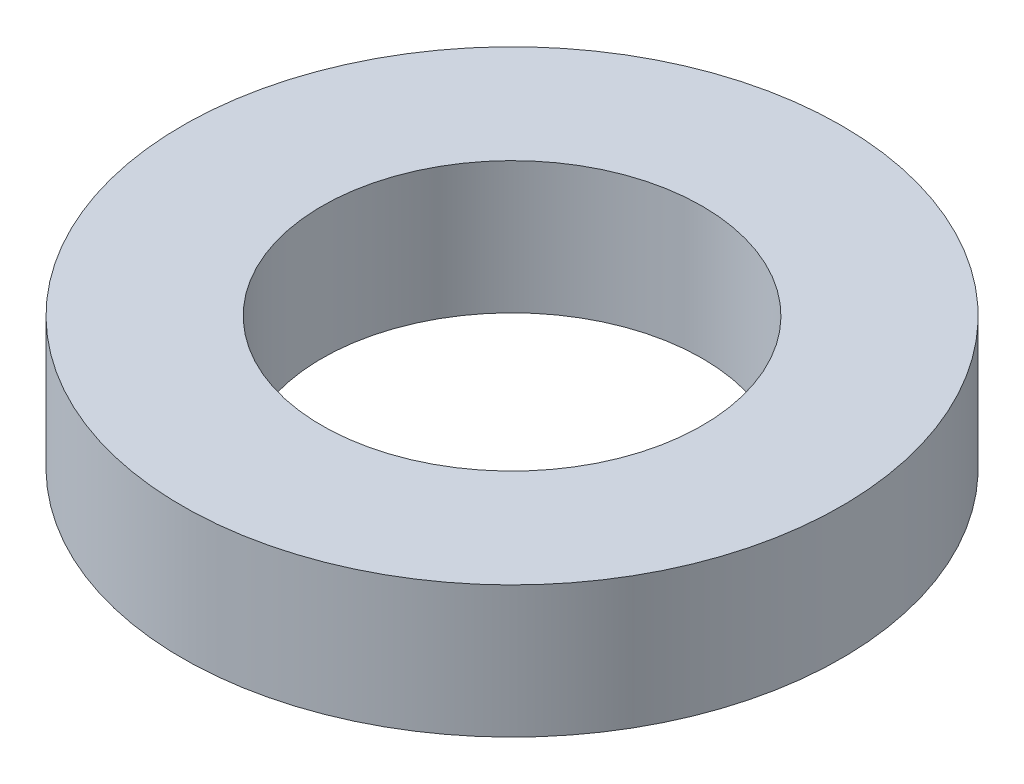
SolidWorks part; units mm, degrees
ref_plane "Front Plane" through (0, 0, 0) normal (0, 0, 1) x (1, 0, 0)
ref_plane "Top Plane" through (0, 0, 0) normal (0, 1, 0) x (1, 0, 0)
ref_plane "Right Plane" through (0, 0, 0) normal (1, 0, 0) x (0, 0, -1)
sketch "Sketch1" plane through (0, 0, 0) normal (0, 1, 0) x (1, 0, 0)
  circle A0 centre (0, 0) radius 65
  dimension "FLANGE_OD" = 130
extrude "Boss-Extrude1" add sketch "Sketch1" along normal blind 26
sketch "Sketch2" plane through (0, 0, 0) normal (0, 1, 0) x (1, 0, 0)
  circle A0 centre (0, 0) radius 37.5
  dimension "BORE_D" = 75
extrude "Cut-Extrude1" cut sketch "Sketch2" along normal through all
sketch "Sketch3" plane through (0, 26, 0) normal (0, 1, 0) x (1, 0, 0)
  circle A0 centre (0, 0) radius 22.7979 construction
  circle A1 centre (-22.7979, 0) radius 3.5655
  dimension "BOLT_D" = 7.131
  dimension "BOLT_PCD" = 45.5957
extrude "Cut-Extrude2" cut sketch "Sketch3" against normal blind 15.7154 rebuild error yes
pattern_circular "CirPattern1" count 4 over 360 rebuild error yes
